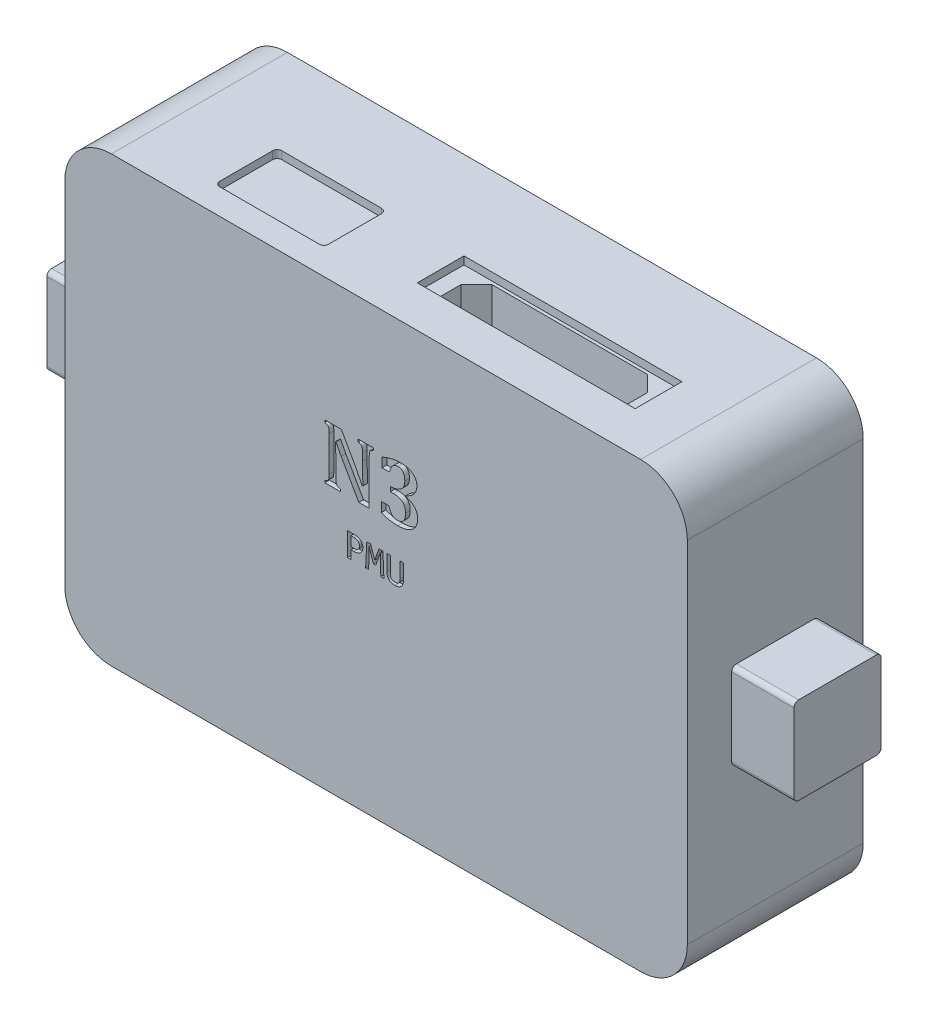
SolidWorks part; units mm, degrees
ref_plane "前视基准面" through (0, 0, 0) normal (0, 0, 1) x (1, 0, 0)
ref_plane "上视基准面" through (0, 0, 0) normal (0, 1, 0) x (1, 0, 0)
ref_plane "右视基准面" through (0, 0, 0) normal (1, 0, 0) x (0, 0, -1)
sketch "Main" plane through (0, 0, 0) normal (0, 0, 1) x (1, 0, 0)
  line L0 (-20, 11.25) -> (-20, -11.25)
  line L1 (0, 0) -> (30.1154, 0) construction
  line L2 (0, -7.3749) -> (0, 9.6594) construction
  line L3 (-17, 14.25) -> (17, 14.25)
  line L4 (20, 11.25) -> (20, -11.25)
  line L5 (-17, -14.25) -> (17, -14.25)
  arc A0 (-20, 11.25) -> (-17, 14.25) centre (-17, 11.25) cw
  arc A1 (20, 11.25) -> (17, 14.25) centre (17, 11.25) ccw
  arc A2 (20, -11.25) -> (17, -14.25) centre (17, -11.25) cw
  arc A3 (-20, -11.25) -> (-17, -14.25) centre (-17, -11.25) ccw
  point P6 (-20, 0)
  point P12 (0, 14.25)
  dimension "D2" = 3
  dimension "D1" = 20
  dimension "D4" = 14.25
extrude "凸台-拉伸1" add sketch "Main" along normal mid plane 11.3
sketch "草图3" plane through (0, 0, 5.65) normal (0, 0, 1) x (1, 0, 0)
  line L0 (0, 0) -> (18.2534, 0) construction
  line L1 (0, 0) -> (0, 13.6083) construction
  text T0 "N3" font "Cambria" height 3.5
  text T1 "PMU" font "Consolas" height 1.5
  dimension "D1" = 3.55
  dimension "D2" = 2
extrude "切除-拉伸3" cut sketch "草图3" against normal blind 0.3
sketch "Up_iBat" plane through (0, 14.25, 0) normal (0, 1, 0) x (1, 0, 0)
  line L0 (-21.0547, 0) -> (21.0547, 0) construction
  line L1 (-11.7, 0) -> (-5.3, 0)
  line L2 (-12, -0.3) -> (-12, -3.7)
  line L3 (-11.7, -4) -> (-5.3, -4)
  line L4 (-5, -0.3) -> (-5, -3.7)
  arc A0 (-12, -0.3) -> (-11.7, 0) centre (-11.7, -0.3) cw
  arc A1 (-12, -3.7) -> (-11.7, -4) centre (-11.7, -3.7) ccw
  arc A2 (-5, -3.7) -> (-5.3, -4) centre (-5.3, -3.7) cw
  arc A3 (-5, -0.3) -> (-5.3, 0) centre (-5.3, -0.3) ccw
  dimension "D3" = 0.3
  dimension "D2" = 12
  dimension "D4" = 7
  dimension "D5" = 4
sketch "草图6" plane through (20, 0, 0) normal (1, 0, 0) x (0, 0, -1)
  line L0 (-2.5, 2.8) -> (2.5, 2.8)
  line L1 (-2.8, 2.5) -> (-2.8, -2.5)
  line L2 (-2.5, -2.8) -> (2.5, -2.8)
  line L3 (2.8, 2.5) -> (2.8, -2.5)
  arc A0 (-2.8, 2.5) -> (-2.5, 2.8) centre (-2.5, 2.5) cw
  arc A1 (-2.8, -2.5) -> (-2.5, -2.8) centre (-2.5, -2.5) ccw
  arc A2 (2.8, -2.5) -> (2.5, -2.8) centre (2.5, -2.5) cw
  arc A3 (2.8, 2.5) -> (2.5, 2.8) centre (2.5, 2.5) ccw
  dimension "D1" = 0.3
  dimension "D2" = 5.6
  dimension "D3" = 5.6
  dimension "D4" = 2.8
  dimension "D5" = 2.8
extrude "凸台-拉伸3" add sketch "草图6" along normal blind 4 contours L0 A3 L3 A2 L2 A1 L1 A0
sketch "草图7" plane through (-20, 0, 0) normal (-1, 0, 0) x (0, 0, 1)
  line L0 (-2.5, 2.8) -> (2.5, 2.8)
  line L1 (-2.8, 2.5) -> (-2.8, -2.5)
  line L2 (-2.5, -2.8) -> (2.5, -2.8)
  line L3 (2.8, 2.5) -> (2.8, -2.5)
  arc A0 (-2.8, 2.5) -> (-2.5, 2.8) centre (-2.5, 2.5) cw
  arc A1 (-2.8, -2.5) -> (-2.5, -2.8) centre (-2.5, -2.5) ccw
  arc A2 (2.8, -2.5) -> (2.5, -2.8) centre (2.5, -2.5) cw
  arc A3 (2.8, 2.5) -> (2.5, 2.8) centre (2.5, 2.5) ccw
  dimension "D1" = 0.3
  dimension "D2" = 5.6
  dimension "D3" = 5.6
  dimension "D4" = 2.8
  dimension "D5" = 2.8
extrude "凸台-拉伸4" add sketch "草图7" along normal blind 4 contours L0 A3 L3 A2 L2 A1 L1 A0
sketch "UP_CAN" plane through (0, 14.25, 0) normal (0, 1, 0) x (-1, 0, 0)
  line L0 (-23.1031, 1.2) -> (5.9887, 1.2) construction
  line L1 (-7, 7.1525) -> (-7, -6.7525) construction
  line L2 (-1, 2.7) -> (-13, 2.7)
  line L3 (-2, 0.2) -> (-12, 0.2)
  line L4 (-1, 2.7) -> (-1, 1.2)
  line L5 (-13, 2.7) -> (-13, 1.2)
  line L6 (-2, 0.2) -> (-1, 1.2)
  line L7 (-12, 0.2) -> (-13, 1.2)
  line L8 (21.0547, 0) -> (-21.0547, 0) construction
  line L9 (0, 0) -> (0, 3)
  line L10 (0, 3) -> (-14, 3)
  line L11 (-14, 3) -> (-14, 0)
  line L12 (-14, 0) -> (0, 0)
  point P7 (-7, 2.7)
  point P10 (-7, 0.2)
  dimension "D1" = 12
  dimension "D2" = 10
  dimension "D3" = 2.5
  dimension "D4" = 1.5
  dimension "D5" = 7
  dimension "D6" = 14
  dimension "D7" = 3
  dimension "D8" = 7
  dimension "D9" = 0.2
extrude "切除-拉伸5" cut sketch "UP_CAN" against normal blind 4 contours L7 L3 L6 L4 L2 L5 region at (7, 14.25, 1.4816)
extrude "切除-拉伸6" cut sketch "UP_CAN<3>" against normal blind 0.5 contours L12 L9 L10 L11
sketch "UP_CAN<3>" plane through (0, 14.25, 0) normal (0, 1, 0) x (-1, 0, 0) same geometry as "UP_CAN"
extrude "切除-拉伸7" cut sketch "Up_iBat" against normal blind 0.5
